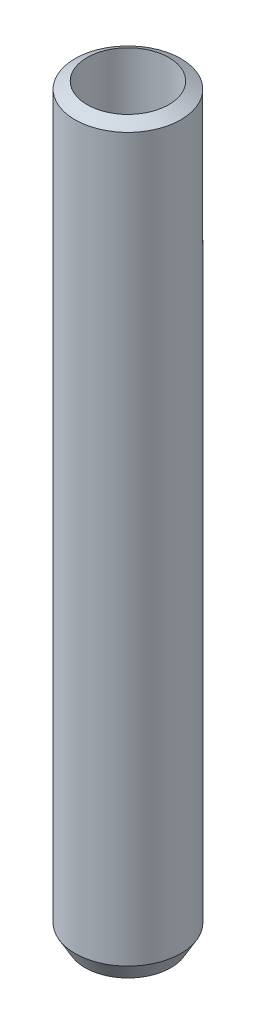
SolidWorks part; units mm, degrees
ref_plane "Front Plane" through (0, 0, 0) normal (0, 0, 1) x (1, 0, 0)
ref_plane "Top Plane" through (0, 0, 0) normal (0, 1, 0) x (1, 0, 0)
ref_plane "Right Plane" through (0, 0, 0) normal (1, 0, 0) x (0, 0, -1)
sketch "Sketch1" plane through (0, 0, 0) normal (0, 1, 0) x (1, 0, 0)
  circle A0 centre (0, 0) radius 15
  dimension "SHAFT_OD" = 30
extrude "Boss-Extrude1" add sketch "Sketch1" along normal blind 212.2712
sketch "Sketch2" plane through (0, 0, 0) normal (0, 1, 0) x (1, 0, 0)
  circle A0 centre (0, 0) radius 11.5706
  dimension "BORE_D" = 23.1413
extrude "Cut-Extrude1" cut sketch "Sketch2" along normal through all
chamfer "Chamfer1" distance 2.8438 angle 60 2 edges at (0, 212.2712, 15) (0, 0, 15) first distance on face at (0, 212.2712, 15) first distance on face at (0, 0, 11.5706)
